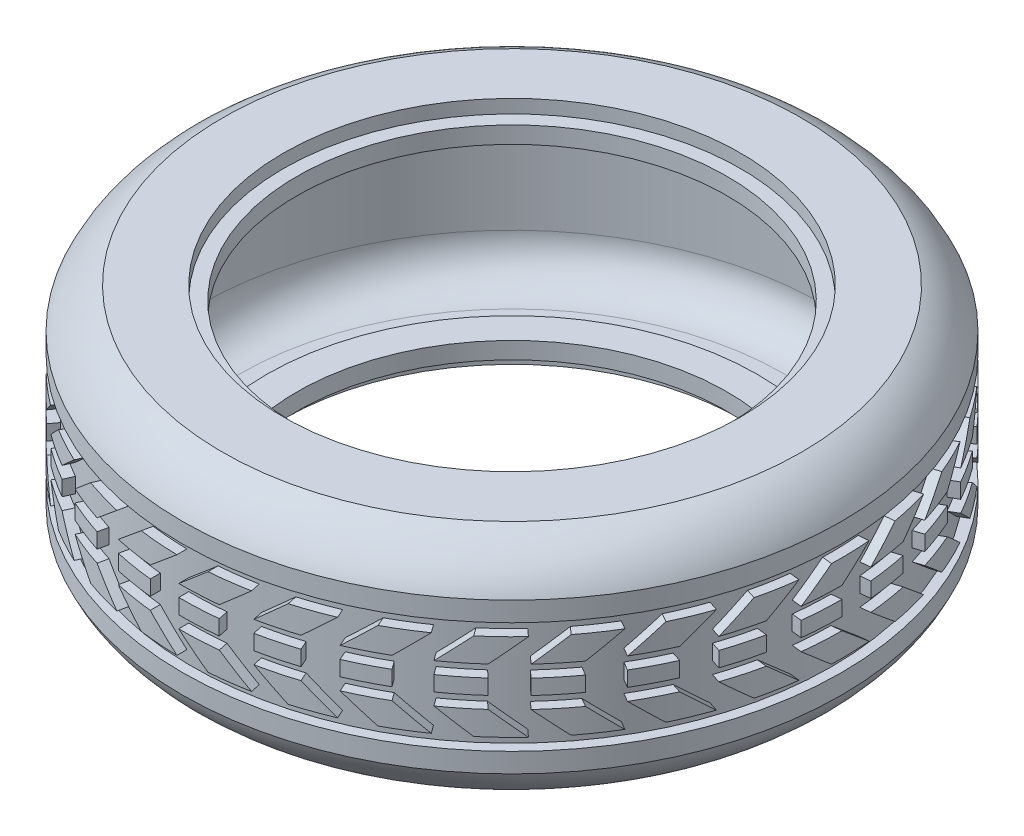
SolidWorks part; units mm, degrees
ref_plane "Front Plane" through (0, 0, 0) normal (0, 0, 1) x (1, 0, 0)
ref_plane "Top Plane" through (0, 0, 0) normal (0, 1, 0) x (1, 0, 0)
ref_plane "Right Plane" through (0, 0, 0) normal (1, 0, 0) x (0, 0, -1)
sketch "Sketch1" plane through (0, 0, 0) normal (0, 0, 1) x (1, 0, 0)
  line L0 (0, -5068.7201) -> (0, 248367.2851) construction
  line L1 (-5068.7201, 0) -> (-465, 0) construction
  line L2 (-320, 151.2727) -> (-320, 126.2727)
  line L3 (-320, 151.2727) -> (-340, 151.2727)
  line L4 (-340, 151.2727) -> (-340, 171.2727)
  line L5 (-340, 171.2727) -> (-430.59, 171.2727)
  line L6 (-490, 111.8627) -> (-490, 82.7981)
  line L7 (-430.59, -171.2727) -> (-340, -171.2727)
  line L8 (-340, -171.2727) -> (-340, -151.2727)
  line L9 (-340, -151.2727) -> (-320, -151.2727)
  line L10 (-465, 86.8627) -> (-465, -86.8627)
  line L11 (-405.59, -146.2727) -> (-365, -146.2727)
  line L12 (-365, -146.2727) -> (-365, -126.2727)
  line L13 (-365, -126.2727) -> (-345, -126.2727)
  line L15 (-345, 126.2727) -> (-365, 126.2727)
  line L16 (-365, 126.2727) -> (-365, 146.2727)
  line L17 (-365, 146.2727) -> (-405.59, 146.2727)
  line L18 (-345, 126.2727) -> (-320, 126.2727)
  line L19 (-345, -126.2727) -> (-320, -126.2727)
  line L20 (-320, -126.2727) -> (-320, -151.2727)
  line L21 (-320, 151.2727) -> (-320, -151.2727) construction
  line L22 (-345, 126.2727) -> (-345, -126.2727) construction
  line L23 (-340, 0) -> (248367.2851, 0) construction
  line L24 (-490, 171.2727) -> (-490, -171.2727) construction
  line L25 (-490, -171.2727) -> (-340, -171.2727) construction
  line L26 (-465, 146.2727) -> (-465, -146.2727) construction
  line L27 (-465, -146.2727) -> (-365, -146.2727) construction
  line L28 (-340, 171.2727) -> (-490, 171.2727) construction
  line L29 (-365, 146.2727) -> (-465, 146.2727) construction
  line L30 (-490, -11.2121) -> (-475.1396, -11.2121)
  line L31 (-490, 82.7981) -> (-475.1396, 82.7981)
  line L33 (-490, 64.7981) -> (-475.1396, 64.7981)
  line L34 (-475.1396, 82.7981) -> (-475.1396, 64.7981)
  line L39 (-490, 29.2121) -> (-475.1396, 29.2121)
  line L41 (-490, 11.2121) -> (-475.1396, 11.2121)
  line L42 (-475.1396, 29.2121) -> (-475.1396, 11.2121)
  line L43 (-475.1396, -29.2121) -> (-475.1396, -11.2121)
  line L44 (-490, -29.2121) -> (-475.1396, -29.2121)
  line L46 (-490, -64.7981) -> (-475.1396, -64.7981)
  line L47 (-475.1396, -82.7981) -> (-475.1396, -64.7981)
  line L48 (-490, -82.7981) -> (-475.1396, -82.7981)
  line L50 (-490, 64.7981) -> (-490, 29.2121)
  line L51 (-490, 11.2121) -> (-490, -11.2121)
  line L52 (-490, -29.2121) -> (-490, -64.7981)
  line L53 (-490, -82.7981) -> (-490, -111.8627)
  arc A1 (-465, -86.8627) -> (-405.59, -146.2727) centre (-405.59, -86.8627) ccw
  arc A3 (-465, 86.8627) -> (-405.59, 146.2727) centre (-405.59, 86.8627) cw
  arc A5 (-430.59, 171.2727) -> (-490, 111.8627) centre (-383.8609, 65.1336) ccw
  arc A6 (-430.59, -171.2727) -> (-490, -111.8627) centre (-383.8609, -65.1336) cw
  dimension "D1" = 320
  dimension "D2" = 20
  dimension "D3" = 20
  dimension "D4" = 20
  dimension "D5" = 20
  dimension "D7" = 25
revolve "Revolve1" add sketch "Sketch1" angle 360 about L0
ref_plane "Plane1" through (0, 0, 500) normal (0, 0, 1) x (1, 0, 0)
sketch "Sketch2" plane through (0, 0, 500) normal (0, 0, 1) x (1, 0, 0)
  line L0 (0, 0) -> (123.8563, 0) construction
  line L1 (57.9923, -82.7981) -> (12.9923, -82.7981)
  line L2 (57.9923, -82.7981) -> (-5.5511, -29.2121)
  line L3 (12.9923, -82.7981) -> (-50.5511, -29.2121)
  line L5 (475.1396, -82.7981) -> (-475.1396, -82.7981) construction
  line L6 (490, -82.7981) -> (-490, -82.7981) construction
  line L7 (475.1396, -29.2121) -> (-475.1396, -29.2121) construction
  line L8 (12.9923, 82.7981) -> (-50.5511, 29.2121)
  line L10 (57.9923, 82.7981) -> (-5.5511, 29.2121)
  line L11 (57.9923, 82.7981) -> (12.9923, 82.7981)
  line L12 (-5.5511, 29.2121) -> (-5.5511, -29.2121)
  line L13 (-50.5511, 29.2121) -> (-50.5511, -29.2121)
  point P17 (0, 0)
  dimension "D1" = 45
extrude "Cut-Extrude1" cut sketch "Sketch2" against normal up to surface (25.0381 mm away) up to face at (475.1396, -29.2121, 0)
pattern_circular "CirPattern1" count 30 over 360 about axis through (0, -5068.7201, 0) along (0, -1, 0) of "Cut-Extrude1"
